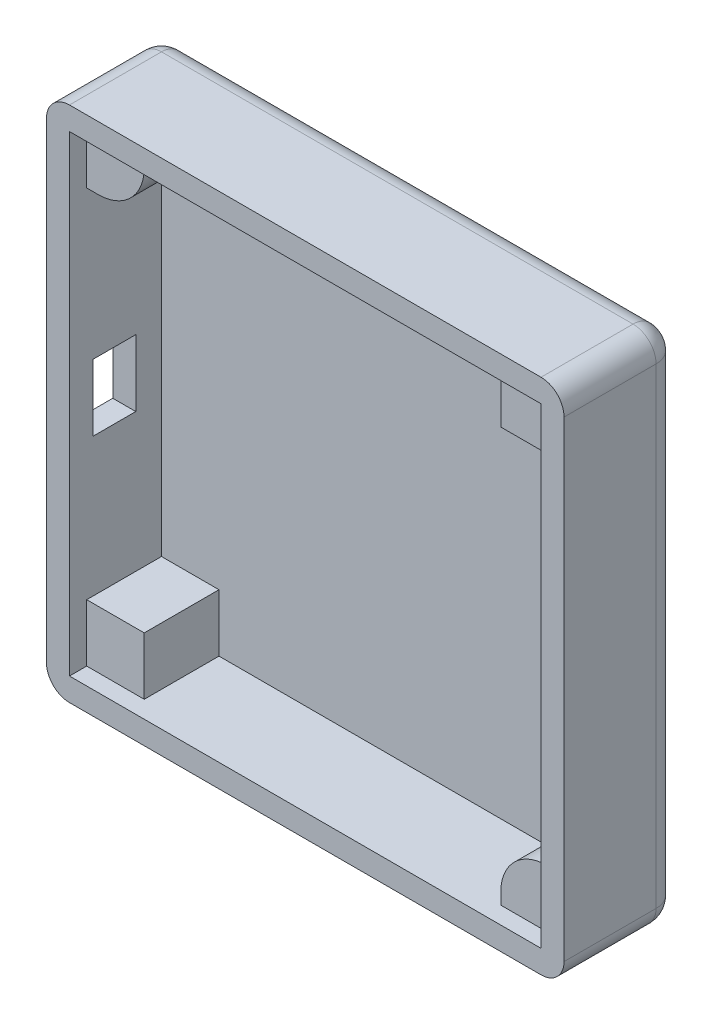
SolidWorks part; units mm, degrees
ref_plane "Piano frontale" through (0, 0, 0) normal (0, 0, 1) x (1, 0, 0)
ref_plane "Piano superiore" through (0, 0, 0) normal (0, 1, 0) x (1, 0, 0)
ref_plane "Piano destro" through (0, 0, 0) normal (1, 0, 0) x (0, 0, -1)
sketch "Schizzo2" plane through (0, 0, 0) normal (0, 0, 1) x (1, 0, 0)
  line L1 (0, 0) -> (45, 0)
  line L2 (0, 0) -> (0, 45)
  line L3 (0, 45) -> (45, 45)
  line L4 (45, 0) -> (45, 45)
  dimension "D1" = 45
  dimension "D2" = 45
extrude "Estrusione-Estrusione2" add sketch "Schizzo2" along normal blind 10
shell "Svuota1" thickness 2 removed face at (22.5, 22.5, 10)
fillet "Raccordo1" radius 2 4 edges at (45, 45, 5) (45, 0, 5) (0, 0, 5) (0, 45, 5)
fillet "Raccordo2" radius 2 8 edges at (44.4142, 0.5858, 0) (22.5, 0, 0) (0.5858, 0.5858, 0) (0, 22.5, 0) (0.5858, 44.4142, 0) (22.5, 45, 0) (44.4142, 44.4142, 0) (45, 22.5, 0)
sketch "Schizzo3" plane through (0, 0, 2) normal (0, 0, 1) x (1, 0, 0)
  line L0 (43, 43) -> (2, 43) construction
  line L1 (2, 43) -> (7, 43)
  line L2 (2, 43) -> (2, 38)
  line L3 (2, 38) -> (7, 38)
  line L4 (7, 43) -> (7, 38)
  line L5 (43, 43) -> (2, 43) construction
  dimension "D1" = 5
  dimension "D2" = 5
extrude "Estrusione-Estrusione3" add sketch "Schizzo3" along normal blind 6.5
sketch "Schizzo4" plane through (0, 0, 2) normal (0, 0, 1) x (1, 0, 0)
  line L1 (43, 2) -> (38, 2)
  line L2 (43, 2) -> (43, 7)
  line L3 (43, 7) -> (38, 7)
  line L4 (38, 2) -> (38, 7)
  dimension "D1" = 5
  dimension "D2" = 5
extrude "Estrusione-Estrusione4" add sketch "Schizzo4" along normal blind 6.5
fillet "Raccordo3" radius 4 2 edges at (38, 7, 5.25) (7, 38, 5.25)
sketch "Schizzo5" plane through (0, 0, 2) normal (0, 0, 1) x (1, 0, 0)
  line L0 (43, 2) -> (43, 43) construction
  line L1 (43, 43) -> (38, 43)
  line L2 (43, 43) -> (43, 38)
  line L3 (43, 38) -> (38, 38)
  line L4 (38, 43) -> (38, 38)
  line L5 (43, 43) -> (7, 43) construction
  line L7 (2, 2) -> (7, 2)
  line L8 (2, 2) -> (2, 7)
  line L9 (2, 7) -> (7, 7)
  line L10 (7, 2) -> (7, 7)
  dimension "D1" = 5
  dimension "D2" = 5
  dimension "D3" = 5
  dimension "D4" = 5
extrude "Estrusione-Estrusione5" add sketch "Schizzo5" along normal blind 6.5 contours L2 L1 L4 L3 | L8 L7 L10 L9
sketch "Schizzo7" plane through (0, 0, 0) normal (-1, 0, 0) x (0, 0, 1)
  line L1 (4.2347, 24.8244) -> (7.9559, 24.8244)
  line L2 (4.2347, 24.8244) -> (4.2347, 19.0329)
  line L3 (4.2347, 19.0329) -> (7.9559, 19.0329)
  line L4 (7.9559, 24.8244) -> (7.9559, 19.0329)
extrude "Taglio-Estrusione1" cut sketch "Schizzo7" against normal blind 3
